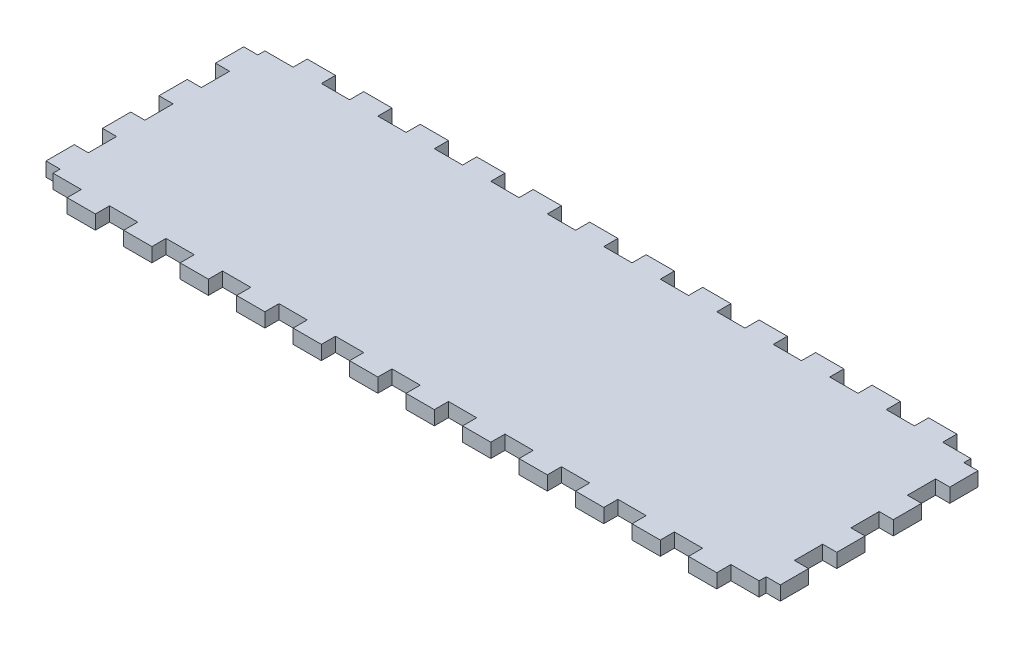
SolidWorks part; units mm, degrees
ref_plane "Front Plane" through (0, 0, 0) normal (0, 0, 1) x (1, 0, 0)
ref_plane "Top Plane" through (0, 0, 0) normal (0, 1, 0) x (1, 0, 0)
ref_plane "Right Plane" through (0, 0, 0) normal (1, 0, 0) x (0, 0, -1)
sketch "Sketch1" plane through (0, 0, 0) normal (0, 1, 0) x (1, 0, 0)
  line L1 (-75, 22.5) -> (75, 22.5)
  line L2 (-75, 22.5) -> (-75, -22.5)
  line L3 (-75, -22.5) -> (75, -22.5)
  line L4 (75, 22.5) -> (75, -22.5)
  line L5 (-75, 22.5) -> (75, -22.5) construction
  line L6 (-75, -22.5) -> (75, 22.5) construction
  point P0 (0, 0)
  dimension "D1" = 45
  dimension "D2" = 150
extrude "Boss-Extrude1" add sketch "Sketch1" along normal blind 3
sketch "Sketch2" plane through (0, 0, 22.5) normal (0, 0, 1) x (1, 0, 0)
  line L0 (0, 0) -> (0, 3) construction
  line L1 (-75, 0) -> (75, 0) construction
  line L2 (-75, 3) -> (75, 3) construction
  line L4 (3, 0) -> (9, 0)
  line L5 (3, 0) -> (3, 3)
  line L6 (3, 3) -> (9, 3)
  line L7 (9, 0) -> (9, 3)
  line L8 (3, 0) -> (9, 3) construction
  line L9 (3, 3) -> (9, 0) construction
  point P10 (6, 1.5)
  dimension "D1" = 3
  dimension "D2" = 6
extrude "Boss-Extrude2" add sketch "Sketch2" along normal blind 3
pattern_linear "LPattern1" count 6 spacing 12 along (1, 0, 0) count 7 spacing 12 along (-1, 0, 0) of "Boss-Extrude2" pattern seed only yes
sketch "Sketch3" plane through (75, 0, 0) normal (1, 0, 0) x (0, 0, -1)
  line L0 (0, 3) -> (0, 0) construction
  line L1 (-22.5, 3) -> (22.5, 3) construction
  line L2 (-22.5, 0) -> (22.5, 0) construction
  line L4 (3, 3) -> (9, 3)
  line L5 (3, 3) -> (3, 0)
  line L6 (3, 0) -> (9, 0)
  line L7 (9, 3) -> (9, 0)
  line L8 (3, 3) -> (9, 0) construction
  line L9 (3, 0) -> (9, 3) construction
  point P10 (6, 1.5)
  dimension "D1" = 6
  dimension "D2" = 3
extrude "Boss-Extrude3" add sketch "Sketch3" along normal blind 3
pattern_linear "LPattern2" count 2 spacing 12 along (0, 0, -1) count 3 spacing 12 along (0, 0, 1) of "Boss-Extrude3"
ref_plane "Plane1" through (0, 0, 0) normal (-1, 0, 0) x (0, 0, 1)
ref_plane "Plane2" through (0, 0, 0) normal (0, 0, -1) x (-1, 0, 0)
mirror "Mirror1" about plane through (0, 0, 0) normal (0, 0, -1) of "LPattern1"
mirror "Mirror2" about plane through (0, 0, 0) normal (-1, 0, 0) of "LPattern2"
